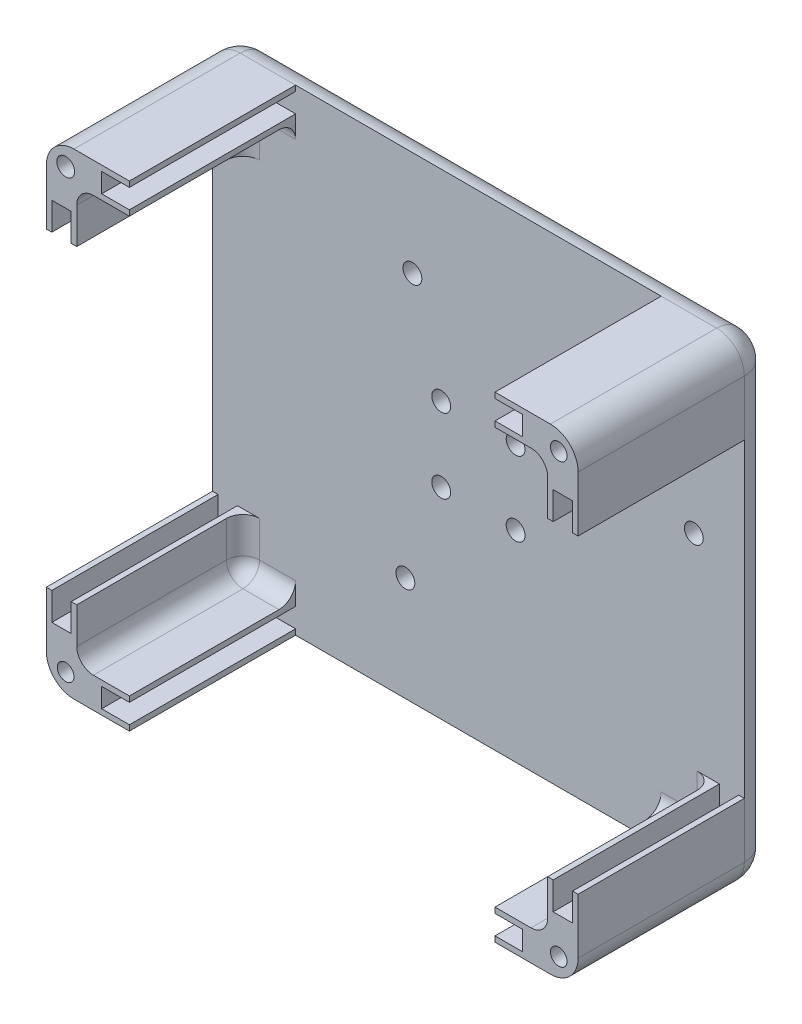
SolidWorks part; units mm, degrees
ref_plane "Plan de face" through (0, 0, 0) normal (0, 0, 1) x (1, 0, 0)
ref_plane "Plan de dessus" through (0, 0, 0) normal (0, 1, 0) x (1, 0, 0)
ref_plane "Plan de droite" through (0, 0, 0) normal (1, 0, 0) x (0, 0, -1)
sketch "Esquisse1" plane through (0, 0, 0) normal (0, 0, 1) x (1, 0, 0)
  line L1 (50.2, -56.1595) -> (-45.8, -56.1595)
  line L2 (50.2, -56.1595) -> (50.2, 29.8405)
  line L3 (50.2, 29.8405) -> (-45.8, 29.8405)
  line L4 (-45.8, -56.1595) -> (-45.8, 29.8405)
  point P0 (0, 0)
  dimension "D1" = 96
  dimension "D2" = 86
extrude "Boss.-Extru.1" add sketch "Esquisse1" along normal blind 5
sketch "trou_support_moteur" plane through (0, 0, 5) normal (0, 0, 1) x (1, 0, 0)
  circle A0 centre (2.2, -13.1595) radius 9.5 construction
  dimension "D1" = 19
sketch "Esquisse33" plane through (0, 0, 5) normal (0, 0, 1) x (1, 0, 0)
  line L1 (-4.5175, -6.4419) -> (8.9175, -6.4419) construction
  line L2 (-4.5175, -6.4419) -> (-4.5175, -19.877) construction
  line L3 (-4.5175, -19.877) -> (8.9175, -19.877) construction
  line L4 (8.9175, -6.4419) -> (8.9175, -19.877) construction
  line L5 (-4.5175, -6.4419) -> (8.9175, -19.877) construction
  line L6 (-4.5175, -19.877) -> (8.9175, -6.4419) construction
  circle A0 centre (2.2, -13.1595) radius 9.5 construction
  point P0 (2.2, -13.1595)
  point P8 (0, 0)
sketch "Esquisse2" plane through (0, 0, 5) normal (0, 0, 1) x (1, 0, 0)
  line L16 (-45.8, 29.8405) -> (-45.8, 14.8405)
  line L17 (-45.8, 29.8405) -> (-45.8, -56.1595) construction
  line L18 (-45.8, 14.8405) -> (-44.8, 14.8405)
  line L19 (-44.8, 14.8405) -> (-44.8, 19.8405)
  line L20 (-44.8, 19.8405) -> (-41.3, 19.8405)
  line L21 (-41.3, 19.8405) -> (-41.3, 14.8405)
  line L22 (-41.3, 14.8405) -> (-40.3, 14.8405)
  line L23 (-40.3, 14.8405) -> (-40.3, 24.3405)
  line L24 (-40.3, 24.3405) -> (-30.8, 24.3405)
  line L25 (-30.8, 24.3405) -> (-30.8, 25.3405)
  line L26 (-30.8, 25.3405) -> (-35.8, 25.3405)
  line L27 (-35.8, 25.3405) -> (-35.8, 28.8405)
  line L28 (-35.8, 28.8405) -> (-30.8, 28.8405)
  line L29 (-30.8, 28.8405) -> (-30.8, 29.8405)
  line L30 (50.2, 29.8405) -> (-45.8, 29.8405) construction
  line L31 (-30.8, 29.8405) -> (-45.8, 29.8405)
  dimension "D2" = 5
  dimension "D3" = 5
  dimension "D4" = 5
  dimension "D5" = 5
  dimension "D6" = 3.5
  dimension "D7" = 3.5
  dimension "D8" = 1
  dimension "D9" = 1
  dimension "D10" = 15
  dimension "D11" = 1
  dimension "D12" = 1
  dimension "D13" = 15
extrude "Boss.-Extru.4" add sketch "Esquisse2" along normal blind 30
fillet "Congé2" radius 5 4 edges at (-45.8, -13.1595, 0) (2.2, -56.1595, 0) (50.2, -13.1595, 0) (2.2, 29.8405, 0)
sketch "Esquisse4" plane through (0, 0, 35) normal (0, 0, 1) x (1, 0, 0)
  line L0 (-45.8, 29.8405) -> (-45.8, 14.8405) construction
  line L1 (-30.8, 29.8405) -> (-45.8, 29.8405) construction
  circle A0 centre (-42.3, 26.3405) radius 1.6
  dimension "D1" = 3.2
  dimension "D2" = 3.5
  dimension "D3" = 3.5
extrude "Enlèv. mat.-Extru.1" cut sketch "Esquisse4" against normal blind 10
sketch "Esquisse14" plane through (0, 0, 5) normal (0, 0, 1) x (1, 0, 0)
  line L0 (-45.8, -56.1595) -> (-45.8, -41.1595)
  line L1 (-45.8, 14.8405) -> (-45.8, -56.1595) construction
  line L2 (-45.8, -41.1595) -> (-44.8, -41.1595)
  line L3 (-44.8, -41.1595) -> (-44.8, -46.1595)
  line L4 (-44.8, -46.1595) -> (-41.3, -46.1595)
  line L5 (-41.3, -46.1595) -> (-41.3, -41.1595)
  line L6 (-41.3, -41.1595) -> (-40.3, -41.1595)
  line L7 (-40.3, -41.1595) -> (-40.3, -50.6595)
  line L8 (-40.3, -50.6595) -> (-30.8, -50.6595)
  line L9 (-30.8, -50.6595) -> (-30.8, -51.6595)
  line L10 (-30.8, -51.6595) -> (-35.8, -51.6595)
  line L11 (-35.8, -51.6595) -> (-35.8, -55.1595)
  line L12 (-35.8, -55.1595) -> (-30.8, -55.1595)
  line L13 (-30.8, -55.1595) -> (-30.8, -56.1595)
  line L14 (-45.8, -56.1595) -> (50.2, -56.1595) construction
  line L15 (-30.8, -56.1595) -> (-45.8, -56.1595)
  dimension "D1" = 15
  dimension "D2" = 15
  dimension "D3" = 5
  dimension "D4" = 5
  dimension "D5" = 3.5
  dimension "D6" = 1
  dimension "D7" = 1
  dimension "D8" = 5
  dimension "D9" = 5
  dimension "D10" = 1
  dimension "D11" = 1
  dimension "D12" = 3.5
sketch "Esquisse21" plane through (0, 0, 5) normal (0, 0, 1) x (1, 0, 0)
  line L0 (-45.8, -56.1595) -> (-45.8, -41.1595)
  line L1 (-45.8, 14.8405) -> (-45.8, -56.1595) construction
  line L2 (-45.8, -41.1595) -> (-44.8, -41.1595)
  line L3 (-44.8, -41.1595) -> (-44.8, -46.1595)
  line L4 (-44.8, -46.1595) -> (-41.3, -46.1595)
  line L5 (-41.3, -46.1595) -> (-41.3, -41.1595)
  line L6 (-41.3, -41.1595) -> (-40.3, -41.1595)
  line L7 (-40.3, -41.1595) -> (-40.3, -50.6595)
  line L8 (-40.3, -50.6595) -> (-30.8, -50.6595)
  line L9 (-30.8, -50.6595) -> (-30.8, -51.6595)
  line L10 (-30.8, -51.6595) -> (-35.8, -51.6595)
  line L11 (-35.8, -51.6595) -> (-35.8, -55.1595)
  line L12 (-35.8, -55.1595) -> (-30.8, -55.1595)
  line L13 (-30.8, -55.1595) -> (-30.8, -56.1595)
  line L14 (-45.8, -56.1595) -> (50.2, -56.1595) construction
  line L15 (-30.8, -56.1595) -> (-45.8, -56.1595)
  dimension "D1" = 15
  dimension "D2" = 15
  dimension "D3" = 5
  dimension "D4" = 5
  dimension "D5" = 5
  dimension "D6" = 5
  dimension "D7" = 1
  dimension "D8" = 1
  dimension "D9" = 3.5
  dimension "D10" = 1
  dimension "D11" = 1
  dimension "D12" = 3.5
extrude "Boss.-Extru.17" add sketch "Esquisse21" along normal blind 30
sketch "Esquisse22" plane through (0, 0, 35) normal (0, 0, 1) x (1, 0, 0)
  line L0 (-45.8, -56.1595) -> (-30.8, -56.1595) construction
  line L1 (-45.8, -41.1595) -> (-45.8, -56.1595) construction
  circle A0 centre (-42.3, -52.6595) radius 1.5
  dimension "D1" = 3
  dimension "D2" = 3.5
  dimension "D3" = 3.5
extrude "Enlèv. mat.-Extru.5" cut sketch "Esquisse22" against normal blind 10
extrude "Boss.-Extru.14" add sketch "Esquisse14" along normal blind 20
sketch "Esquisse16" plane through (0, 0, 5) normal (0, 0, 1) x (1, 0, 0)
  line L0 (50.2, 29.8405) -> (35.2, 29.8405)
  line L1 (50.2, 29.8405) -> (-30.8, 29.8405) construction
  line L2 (35.2, 29.8405) -> (35.2, 28.8405)
  line L3 (35.2, 28.8405) -> (40.2, 28.8405)
  line L4 (40.2, 28.8405) -> (40.2, 25.3405)
  line L5 (40.2, 25.3405) -> (35.2, 25.3405)
  line L6 (35.2, 25.3405) -> (35.2, 24.3405)
  line L7 (35.2, 24.3405) -> (44.7, 24.3405)
  line L8 (44.7, 24.3405) -> (44.7, 14.8405)
  line L9 (44.7, 14.8405) -> (45.7, 14.8405)
  line L10 (45.7, 14.8405) -> (45.7, 19.8405)
  line L11 (45.7, 19.8405) -> (49.2, 19.8405)
  line L12 (49.2, 19.8405) -> (49.2, 14.8405)
  line L13 (49.2, 14.8405) -> (50.2, 14.8405)
  line L14 (50.2, -56.1595) -> (50.2, 29.8405) construction
  line L15 (50.2, 14.8405) -> (50.2, 29.8405)
  dimension "D1" = 15
  dimension "D2" = 15
  dimension "D3" = 5
  dimension "D4" = 5
  dimension "D5" = 5
  dimension "D6" = 5
  dimension "D7" = 1
  dimension "D8" = 1
  dimension "D9" = 3.5
  dimension "D10" = 1
  dimension "D11" = 1
  dimension "D12" = 3.5
extrude "Boss.-Extru.15" add sketch "Esquisse16" along normal blind 30
sketch "Esquisse17" plane through (0, 0, 35) normal (0, 0, 1) x (1, 0, 0)
  line L0 (50.2, 29.8405) -> (35.2, 29.8405) construction
  line L1 (50.2, 14.8405) -> (50.2, 29.8405) construction
  circle A0 centre (46.7, 26.3405) radius 1.5
  dimension "D1" = 3
  dimension "D2" = 3.5
  dimension "D3" = 3.5
extrude "Enlèv. mat.-Extru.3" cut sketch "Esquisse17" against normal blind 10
sketch "Esquisse18" plane through (0, 0, 5) normal (0, 0, 1) x (1, 0, 0)
  line L0 (50.2, -56.1595) -> (50.2, -41.1595)
  line L1 (50.2, -56.1595) -> (50.2, 14.8405) construction
  line L2 (50.2, -41.1595) -> (49.2, -41.1595)
  line L3 (49.2, -41.1595) -> (49.2, -46.1595)
  line L4 (49.2, -46.1595) -> (45.7, -46.1595)
  line L5 (45.7, -46.1595) -> (45.7, -41.1595)
  line L6 (45.7, -41.1595) -> (44.7, -41.1595)
  line L7 (44.7, -41.1595) -> (44.7, -50.6595)
  line L8 (44.7, -50.6595) -> (35.2, -50.6595)
  line L9 (35.2, -50.6595) -> (35.2, -51.6595)
  line L10 (35.2, -51.6595) -> (40.2, -51.6595)
  line L11 (40.2, -51.6595) -> (40.2, -55.1595)
  line L12 (40.2, -55.1595) -> (35.2, -55.1595)
  line L13 (35.2, -55.1595) -> (35.2, -56.1595)
  line L14 (-30.8, -56.1595) -> (50.2, -56.1595) construction
  line L15 (35.2, -56.1595) -> (50.2, -56.1595)
  dimension "D1" = 15
  dimension "D2" = 15
  dimension "D3" = 5
  dimension "D4" = 5
  dimension "D5" = 5
  dimension "D6" = 5
  dimension "D7" = 3.5
  dimension "D8" = 1
  dimension "D9" = 1
  dimension "D10" = 1
  dimension "D11" = 1
  dimension "D12" = 3.5
extrude "Boss.-Extru.16" add sketch "Esquisse18" along normal blind 30
sketch "Esquisse19" plane through (0, 0, 35) normal (0, 0, 1) x (1, 0, 0)
  line L0 (35.2, -56.1595) -> (50.2, -56.1595) construction
  line L1 (50.2, -56.1595) -> (50.2, -41.1595) construction
  circle A0 centre (46.7, -52.6595) radius 1.5
  dimension "D1" = 3
  dimension "D2" = 3.5
  dimension "D3" = 3.5
extrude "Enlèv. mat.-Extru.4" cut sketch "Esquisse19" against normal blind 10
fillet "Congé6" radius 5 8 edges at (48.7355, 28.3761, 1.4645) (48.7355, -54.695, 1.4645) (-44.3355, -54.695, 1.4645) (-44.3355, 28.3761, 1.4645) (50.2, 29.8405, 20) (50.2, -56.1595, 20) (-45.8, -56.1595, 20) (-45.8, 29.8405, 20)
sketch "EsquisseEntretoise1" plane through (0, 0, 5) normal (0, 0, 1) x (1, 0, 0)
  line L0 (35.2, 29.8405) -> (-30.8, 29.8405) construction
  line L1 (-45.8, 14.8405) -> (-45.8, -41.1595) construction
  circle A0 centre (-9.71, 10.9605) radius 2 construction
  dimension "D1" = 4
  dimension "D2" = 18.88
  dimension "D3" = 36.09
sketch "EsquisseEntretoise2" plane through (0, 0, 5) normal (0, 0, 1) x (1, 0, 0)
  line L0 (-30.8, -56.1595) -> (35.2, -56.1595) construction
  line L2 (-45.8, 14.8405) -> (-45.8, -41.1595) construction
  circle A0 centre (-10.98, -37.2995) radius 2 construction
  dimension "D1" = 4
  dimension "D2" = 18.86
  dimension "D3" = 34.82
sketch "EsquisseEntretoise3" plane through (0, 0, 5) normal (0, 0, 1) x (1, 0, 0)
  line L0 (50.2, -41.1595) -> (50.2, 14.8405) construction
  line L1 (35.2, 29.8405) -> (-30.8, 29.8405) construction
  circle A0 centre (41.09, -4.2795) radius 2 construction
  dimension "D1" = 4
  dimension "D2" = 9.11
  dimension "D3" = 34.12
fillet "Congé14" radius 3 12 edges at (-35.55, -50.6595, 5) (-40.3, -45.9095, 5) (39.95, -50.6595, 5) (44.7, -45.9095, 5) (44.7, 19.5905, 5) (39.95, 24.3405, 5) (-40.3, 19.5905, 5) (-35.55, 24.3405, 5) (-40.3, -50.6595, 20) (44.7, -50.6595, 20) (-40.3, 24.3405, 20) (44.7, 24.3405, 20)
hole_wizard "TrouM3" positions "Esquisse34" profile "Esquisse35" hole size "M3" standard "ISO" end condition up to next
sketch "Esquisse34" plane through (0, 0, 5) normal (0, 0, 1) x (1, 0, 0)
  point P0 (-9.71, 10.9605)
  point P3 (41.09, -4.2795)
  point P6 (-10.98, -37.2995)
  point P9 (-4.5175, -19.877)
  point P12 (-4.5175, -6.4419)
  point P15 (8.9175, -6.4419)
  point P18 (8.9175, -19.877)
sketch "Esquisse35" plane through (-9.71, 10.9605, 5) normal (1, 0, 0) x (0, -1, 0)
  line L0 (0, 0) -> (0, 5)
  line L1 (0, 5) -> (1.7, 5)
  line L2 (1.7, 5) -> (1.7, 0)
  line L5 (1.7, 0) -> (0, 0)
  line L11 (0, -6.35) -> (0, 107.95) construction
  dimension "Diamètre du perçage jusqu'au prochain" = 3.4
  dimension "Profondeur du perçage jusqu'au prochain" = 5
